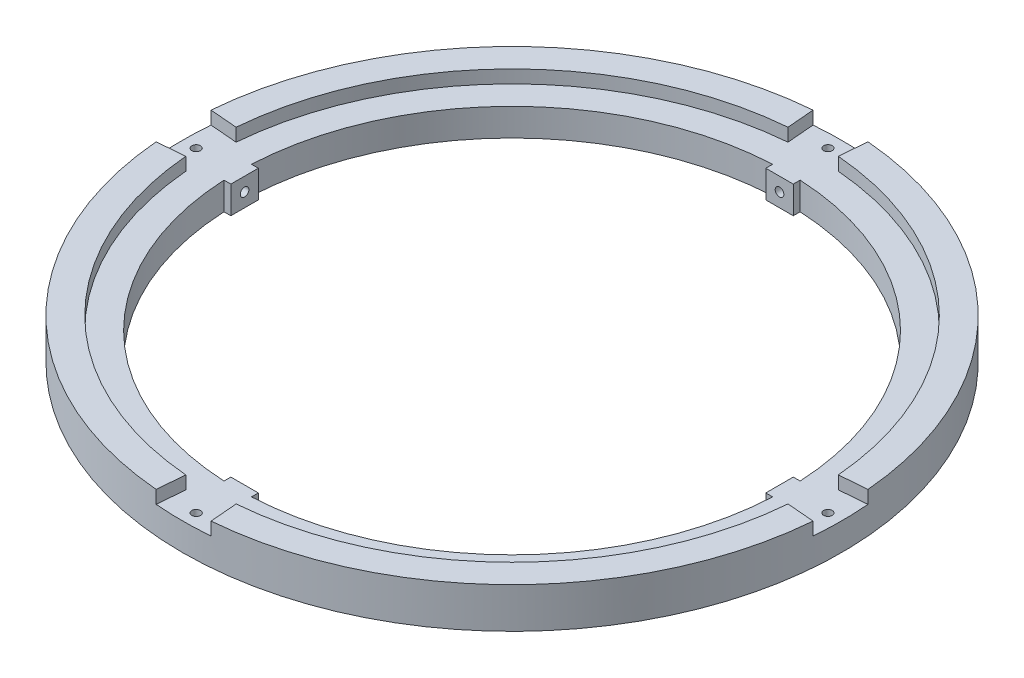
SolidWorks part; units mm, degrees
ref_plane "Front Plane" through (0, 0, 0) normal (0, 0, 1) x (1, 0, 0)
ref_plane "Top Plane" through (0, 0, 0) normal (0, 1, 0) x (1, 0, 0)
ref_plane "Right Plane" through (0, 0, 0) normal (1, 0, 0) x (0, 0, -1)
sketch "Sketch1" plane through (0, 0, 0) normal (0, 1, 0) x (1, 0, 0)
  circle A0 centre (0, 0) radius 139.7
  circle A1 centre (0, 0) radius 127
  circle A2 centre (0, 0) radius 152.4
extrude "Boss-Extrude1" add sketch "Sketch1" along normal blind 18.7 contours A2 A0 region at (-148.0895, 0, 0)
extrude "Boss-Extrude2" add sketch "Sketch1<3>" along normal blind 12.7 contours A0 A1 region at (-135.7487, 0, 0)
sketch "Sketch1<3>" plane through (0, 0, 0) normal (0, 1, 0) x (1, 0, 0) same geometry as "Sketch1"
sketch "Sketch2" plane through (0, 0, 0) normal (0, -1, 0) x (1, 0, 0)
  line L0 (0, -127) -> (0, -123.6662)
  line L1 (-6.35, -123.6662) -> (6.35, -123.6662)
  line L2 (6.35, -123.6662) -> (6.35, -125.2537)
  line L3 (6.35, -125.2537) -> (-6.35, -125.2537)
  line L4 (-6.35, -125.2537) -> (-6.35, -123.6662)
  line L5 (-6.35, -123.6662) -> (-6.35, -126.8412)
  line L6 (6.35, -123.6662) -> (6.35, -126.8412)
  line L7 (-123.6662, -6.35) -> (-126.8412, -6.35)
  line L8 (-123.6662, 6.35) -> (-126.8412, 6.35)
  line L9 (-123.6662, 6.35) -> (-123.6662, -6.35)
  line L10 (-6.35, 123.6662) -> (-6.35, 126.8412)
  line L11 (6.35, 123.6662) -> (6.35, 126.8412)
  line L12 (6.35, 123.6662) -> (-6.35, 123.6662)
  line L13 (123.6662, 6.35) -> (126.8412, 6.35)
  line L14 (123.6662, -6.35) -> (126.8412, -6.35)
  line L15 (123.6662, -6.35) -> (123.6662, 6.35)
  circle A0 centre (0, 0) radius 127 construction
  point P9 (0, -123.6662)
  point P28 (0, 0)
  circle M2 centre (0, 0) radius 127
  dimension "D1" = 1.5875
  dimension "D2" = 1.5875
  dimension "D4" = 12.7
  dimension "D3" = 4
extrude "Boss-Extrude3" add sketch "Sketch2" against normal blind 12.7 contours L9 L8 L7 M2 | L12 L11 L10 M2 | L15 L14 L13 M2 | L6 L3 L0 M2 | L3 L2 L1 L0 | L4 L3 L0 L1 | L3 L5 L0 M2 region at (-3.1254, 0, -126.101) region at (3.1254, 0, -126.101) region at (-3.175, 0, -124.4599) region at (3.175, 0, -124.4599) region at (-125.3069, 0, 0) region at (125.3069, 0, 0) region at (0, 0, 125.3069)
sketch "Sketch3" plane through (-123.6662, 0, 0) normal (1, 0, 0) x (0, 0, -1)
  line L0 (0, 12.7) -> (0, 0)
  line L1 (-6.35, 12.7) -> (6.35, 12.7) construction
  line L2 (-6.35, 0) -> (6.35, 0) construction
  circle A0 centre (0, 6.35) radius 2
extrude "Cut-Extrude1" cut sketch "Sketch3" against normal blind 25.4 contours L0 A0 | L0 A0 region at (-123.6662, 6.35, -0.8488) region at (-123.6662, 6.35, 0.8488)
pattern_circular "CirPattern1" count 4 every 90 about axis through (0, 12.7, 0) along (0, 1, 0) of "Cut-Extrude1"
sketch "Sketch4" plane through (0, 18.7, 0) normal (0, 1, 0) x (1, 0, 0)
  line L0 (-139.7, 0) -> (-152.4, 0)
  line L1 (-151.8699, -12.7) -> (0, 0)
  line L2 (0, 0) -> (-151.8708, 12.689)
  circle A0 centre (0, 0) radius 139.7 construction
  circle A1 centre (0, 0) radius 152.4 construction
  arc A2 (-151.8699, -12.7) -> (-151.8708, 12.689) centre (0, 0) cw
  circle A3 centre (0, 0) radius 139.7
  circle M4 centre (0, 0) radius 139.7
  circle M5 centre (0, 0) radius 152.4
  dimension "D1" = 152.4
  dimension "D2" = 12.7
  dimension "D3" = 12.7
extrude "Cut-Extrude4" cut sketch "Sketch4" against normal blind 6 contours L1 L0 M5 M4 | L2 L0 M4 M5 region at (-145.9725, 18.7, 6.0928) region at (-145.9728, 18.7, -6.0875)
sketch "Sketch5" plane through (0, 12.7, 0) normal (0, 1, 0) x (1, 0, 0)
  line L0 (-152.4, -0.0055) -> (-146.05, -0.0055)
  arc A0 (-151.8708, 12.689) -> (-151.8699, -12.7) centre (0, 0) ccw construction
  circle A1 centre (-146.05, -0.0055) radius 2
  dimension "D1" = 6.35
extrude "Cut-Extrude5" cut sketch "Sketch5" against normal blind 12.7 contours A1
pattern_circular "CirPattern2" count 4 every 90 about axis through (0, 18.7, 0) along (0, 1, 0) of "Cut-Extrude4", "Cut-Extrude5"
